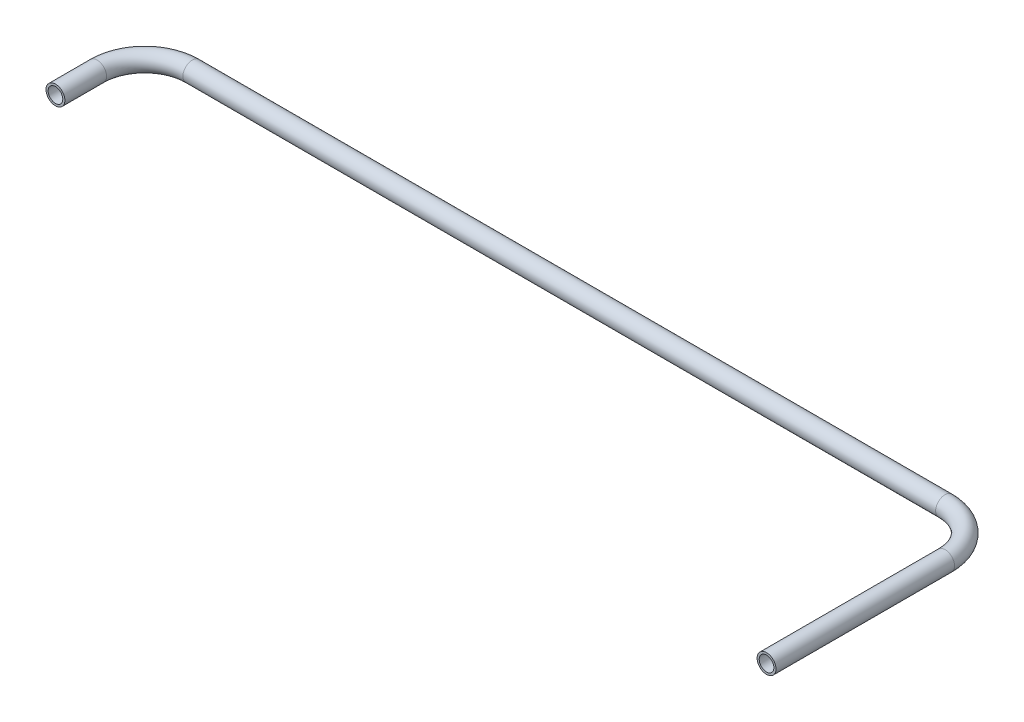
SolidWorks part; units mm, degrees
ref_plane "Front Plane" through (0, 0, 0) normal (0, 0, 1) x (1, 0, 0)
ref_plane "Top Plane" through (0, 0, 0) normal (0, 1, 0) x (1, 0, 0)
ref_plane "Right Plane" through (0, 0, 0) normal (1, 0, 0) x (0, 0, -1)
sketch "Sketch1" plane through (0, 0, 0) normal (0, 1, 0) x (1, 0, 0)
  line L0 (0, 0) -> (0, 14)
  line L1 (16, 30) -> (269, 30)
  line L2 (285, 14) -> (285, -46)
  arc A0 (269, 30) -> (285, 14) centre (269, 14) cw
  arc A1 (0, 14) -> (16, 30) centre (16, 14) cw
  dimension "D1" = 16
  dimension "D2" = 16
  dimension "D3" = 14
  dimension "D4" = 60
  dimension "D5" = 285
sketch "Sketch2" plane through (0, 0, 0) normal (0, 0, 1) x (1, 0, 0)
  circle A0 centre (0, 0) radius 3.175
  dimension "D1" = 6.35
sweep "Sweep-Thin1" add profiles "Sketch2" path "Sketch1" parameters "D1"=0.7112
